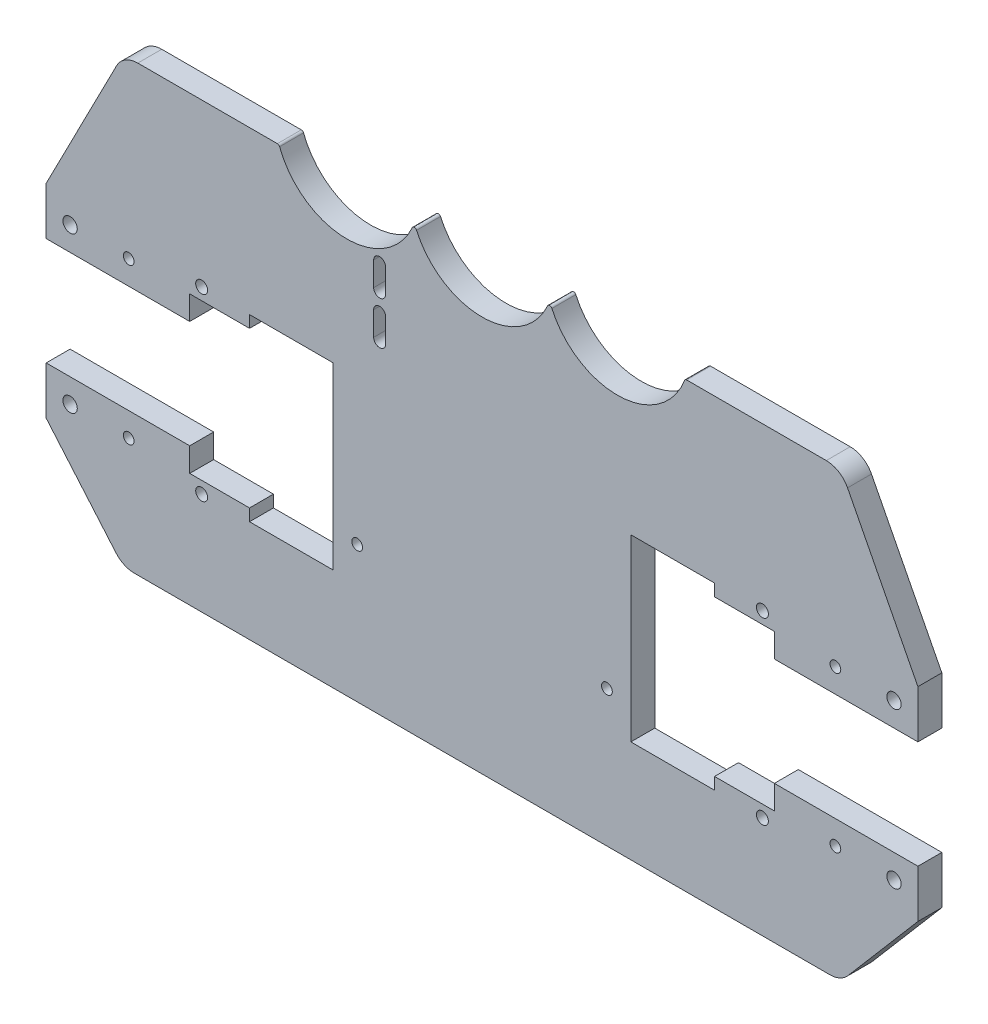
SolidWorks part; units mm, degrees
ref_plane "Plan de face" through (0, 0, 0) normal (0, 0, 1) x (1, 0, 0)
ref_plane "Plan de dessus" through (0, 0, 0) normal (0, 1, 0) x (1, 0, 0)
ref_plane "Plan de droite" through (0, 0, 0) normal (1, 0, 0) x (0, 0, -1)
sketch "Esquisse3" plane through (0, 0, 0) normal (0, 0, 1) x (1, 0, 0)
  line L0 (-182.2, 42.5) -> (-150, 105.2)
  line L1 (-182.2, 42.5) -> (182.2, 42.5)
  line L2 (-182.2, 42.5) -> (-182.2, -42.5)
  line L3 (-182.2, -42.5) -> (182.2, -42.5)
  line L4 (182.2, 42.5) -> (182.2, -42.5)
  line L5 (-150, 105.2) -> (150, 105.2)
  line L6 (-150, 105.2) -> (-150, 42.5)
  line L7 (-150, 42.5) -> (150, 42.5)
  line L8 (150, 105.2) -> (150, 42.5)
  line L9 (-150, -80.2) -> (150, -80.2)
  line L10 (-150, -80.2) -> (-150, -42.5)
  line L11 (-150, -42.5) -> (150, -42.5)
  line L12 (150, -80.2) -> (150, -42.5)
  line L13 (150, 105.2) -> (182.2, 42.5)
  line L14 (182.2, -42.5) -> (150, -80.2)
  line L15 (-150, -80.2) -> (-182.2, -42.5)
  dimension "D1" = 85
  dimension "D2" = 300
  dimension "D3" = 300
  dimension "D4" = 32.2
  dimension "D5" = 0
  dimension "D6" = 32.2
  dimension "D7" = 37.7
  dimension "D8" = 62.7
  dimension "D9" = 150
  dimension "D10" = 42.5
extrude "Boss.-Extru.1" add sketch "Esquisse3" along normal blind 10 contours L4 L1 L2 L3 | L8 L5 L6 L1 | L9 L12 L3 L10 | L6 L0 L1 | L15 L10 L3 | L14 L3 L12 | L13 L8 L1 region at (-160.7333, 63.4, 0) region at (0, 0, 0) region at (0, 73.85, 0) region at (-160.7333, -55.0667, 0) region at (160.7333, 63.4, 0) region at (0, -61.35, 0) region at (160.7333, -55.0667, 0)
sketch "Esquisse4" plane through (0, 0, 10) normal (0, 0, 1) x (1, 0, 0)
  line L1 (-182.2, 32.5) -> (-97.2, 32.5)
  line L2 (-182.2, 32.5) -> (-182.2, -32.5)
  line L3 (-182.2, -32.5) -> (-97.2, -32.5)
  line L4 (-97.2, 32.5) -> (-97.2, -32.5)
  line L5 (-97.2, -37.5) -> (-62.2, -37.5)
  line L6 (-97.2, -37.5) -> (-97.2, 37.5)
  line L7 (-97.2, 37.5) -> (-62.2, 37.5)
  line L8 (-62.2, -37.5) -> (-62.2, 37.5)
  line L9 (182.2, 32.5) -> (97.2, 32.5)
  line L10 (182.2, 32.5) -> (182.2, -32.5)
  line L11 (182.2, -32.5) -> (97.2, -32.5)
  line L12 (97.2, 32.5) -> (97.2, -32.5)
  line L13 (97.2, 37.5) -> (62.2, 37.5)
  line L14 (97.2, 37.5) -> (97.2, -37.5)
  line L15 (97.2, -37.5) -> (62.2, -37.5)
  line L16 (62.2, 37.5) -> (62.2, -37.5)
  line L17 (-182.2, 32.5) -> (-122.2, 32.5)
  line L18 (-182.2, 32.5) -> (-182.2, 22.5)
  line L19 (-182.2, 22.5) -> (-122.2, 22.5)
  line L20 (-122.2, 32.5) -> (-122.2, 22.5)
  line L21 (-182.2, -32.5) -> (-122.2, -32.5)
  line L22 (-182.2, -32.5) -> (-182.2, -22.5)
  line L23 (-182.2, -22.5) -> (-122.2, -22.5)
  line L24 (-122.2, -32.5) -> (-122.2, -22.5)
  line L25 (182.2, 32.5) -> (122.2, 32.5)
  line L26 (182.2, 32.5) -> (182.2, 22.5)
  line L27 (182.2, 22.5) -> (122.2, 22.5)
  line L28 (122.2, 32.5) -> (122.2, 22.5)
  line L29 (182.2, -32.5) -> (122.2, -32.5)
  line L30 (182.2, -32.5) -> (182.2, -22.5)
  line L31 (182.2, -22.5) -> (122.2, -22.5)
  line L32 (122.2, -32.5) -> (122.2, -22.5)
  line L34 (-182.2, 42.5) -> (-182.2, -42.5) construction
  line M16 (182.2, -42.5) -> (182.2, 42.5)
  line M20 (-182.2, 42.5) -> (-182.2, -42.5)
  dimension "D1" = 85
  dimension "D2" = 5
  dimension "D3" = 5
  dimension "D4" = 35
  dimension "D5" = 85
  dimension "D6" = 85
  dimension "D7" = 35
  dimension "D8" = 85
  dimension "D9" = 5
  dimension "D10" = 5
  dimension "D11" = 0
  dimension "D12" = 60
  dimension "D13" = 10
  dimension "D14" = 10
  dimension "D15" = 0
  dimension "D16" = 10
  dimension "D17" = 10
  dimension "D18" = 60
  dimension "D19" = 10
  dimension "D20" = 10
  dimension "D21" = 0
  dimension "D22" = 10
  dimension "D23" = 10
extrude "Enlèv. mat.-Extru.1" cut sketch "Esquisse4" against normal blind 10 contours L4 L1 L3 M20 | L5 L8 L7 L6 L4 | L13 L16 L15 L14 L12 | L9 L12 L11 M16 region at (-136.2318, 0, 10) region at (-79.7, 0, 10) region at (136.2318, 0, 10) region at (79.7, 0, 10)
sketch "Esquisse5" plane through (0, 0, 10) normal (0, 0, 1) x (1, 0, 0)
  line L1 (-150, 105.2) -> (150, 105.2) construction
  arc A0 (28.2843, 105.2) -> (-28.2843, 105.2) centre (0, 115.2) cw
  arc A1 (-28.2843, 105.2) -> (-84.8528, 105.2) centre (-56.5685, 115.2) cw
  arc A2 (28.2843, 105.2) -> (84.8528, 105.2) centre (56.5685, 115.2) ccw
  dimension "D1" = 10
  dimension "D2" = 30
  dimension "D3" = 30
  dimension "D6" = 30
  dimension "D4" = 10
  dimension "D5" = 10
extrude "Enlèv. mat.-Extru.2" cut sketch "Esquisse5" against normal blind 10 and the other way through all
sketch "Esquisse11" plane through (0, 0, 10) normal (0, 0, 1) x (1, 0, 0)
  line L0 (182.2, 42.5) -> (182.2, 22.5) construction
  line L1 (-182.2, 42.5) -> (-162.2, 42.5)
  line L2 (-182.2, 42.5) -> (-182.2, 22.5)
  line L3 (-182.2, 22.5) -> (-162.2, 22.5)
  line L4 (-162.2, 42.5) -> (-162.2, 22.5)
  line L6 (182.2, -22.5) -> (182.2, -42.5) construction
  line L7 (-182.2, -22.5) -> (-162.2, -22.5)
  line L8 (-182.2, -22.5) -> (-182.2, -42.5)
  line L9 (-182.2, -42.5) -> (-162.2, -42.5)
  line L10 (-162.2, -22.5) -> (-162.2, -42.5)
  line L11 (182.2, 22.5) -> (122.2, 22.5) construction
  line L12 (162.2, 42.5) -> (182.2, 42.5)
  line L13 (162.2, 42.5) -> (162.2, 22.5)
  line L14 (162.2, 22.5) -> (182.2, 22.5)
  line L15 (182.2, 42.5) -> (182.2, 22.5)
  line L16 (162.2, -22.5) -> (182.2, -22.5)
  line L17 (162.2, -22.5) -> (162.2, -42.5)
  line L18 (162.2, -42.5) -> (182.2, -42.5)
  line L19 (182.2, -22.5) -> (182.2, -42.5)
  line L20 (-182.2, -22.5) -> (-182.2, -42.5) construction
  line L22 (-182.2, 42.5) -> (-182.2, 22.5) construction
  line L23 (182.2, -22.5) -> (122.2, -22.5) construction
  line L24 (-182.2, -22.5) -> (-122.2, -22.5) construction
  line L25 (-182.2, 22.5) -> (-122.2, 22.5) construction
  point P24 (172.2, 22.5)
  dimension "D1" = 20
  dimension "D2" = 20
  dimension "D3" = 0
  dimension "D4" = 0
  dimension "D5" = 20
  dimension "D6" = 20
  dimension "D7" = 0
  dimension "D8" = 0
  dimension "D9" = 20
  dimension "D10" = 20
  dimension "D11" = 20
  dimension "D12" = 20
  dimension "D13" = 0
  dimension "D14" = 0
  dimension "D15" = 0
  dimension "D16" = 0
sketch "Esquisse10" plane through (0, 0, 10) normal (0, 0, 1) x (1, 0, 0)
  line L1 (-182.2, 42.5) -> (-162.2, 42.5) construction
  line L2 (162.2, -22.5) -> (162.2, -42.5) construction
  line L3 (-182.2, 22.5) -> (-162.2, 22.5) construction
  line L4 (-162.2, 42.5) -> (-162.2, 22.5) construction
  line L5 (-182.2, -22.5) -> (-182.2, -42.5) construction
  line L6 (-182.2, -22.5) -> (-162.2, -22.5) construction
  line L8 (162.2, 42.5) -> (182.2, 42.5) construction
  line L10 (162.2, 42.5) -> (162.2, 22.5) construction
  line L11 (182.2, -22.5) -> (182.2, -42.5) construction
  line L12 (162.2, -22.5) -> (182.2, -22.5) construction
  line L13 (162.2, -42.5) -> (182.2, -42.5) construction
  line L15 (-162.2, -22.5) -> (-162.2, -42.5) construction
  circle A1 centre (-147.7, 32.5) radius 2.25
  circle A2 centre (-172.2, 32.5) radius 3
  circle A3 centre (-172.2, -32.5) radius 3
  circle A4 centre (-147.7, -32.5) radius 2.25
  circle A6 centre (172.2, 32.5) radius 3
  circle A8 centre (147.7, 32.5) radius 2.25
  circle A9 centre (172.2, -32.5) radius 3
  circle A10 centre (147.7, -32.5) radius 2.25
  dimension "D4" = 4.5
  dimension "D9" = 6
  dimension "D10" = 6
  dimension "D17" = 6
  dimension "D18" = 4.5
  dimension "D24" = 4.5
  dimension "D28" = 6
  dimension "D35" = 4.5
  dimension "D15" = 14.5
  dimension "D16" = 14.5
  dimension "D5" = 14.5
  dimension "D13" = 14.5
  dimension "D6" = 10
  dimension "D7" = 10
  dimension "D8" = 10
  dimension "D11" = 10
  dimension "D12" = 10
  dimension "D14" = 10
  dimension "D22" = 10
  dimension "D23" = 10
  dimension "D27" = 10
  dimension "D29" = 10
  dimension "D30" = 10
  dimension "D34" = 10
extrude "Enlèv. mat.-Extru.3" cut sketch "Esquisse10" against normal blind 10
sketch "Esquisse13" plane through (0, 0, 10) normal (0, 0, 1) x (1, 0, 0)
  line L0 (-62.2, -37.5) -> (-62.2, 37.5) construction
  line L1 (-62, 1.8) -> (62, 1.8)
  line L2 (-62, 1.8) -> (-62, -8.2)
  line L3 (-62, -8.2) -> (62, -8.2)
  line L4 (62, 1.8) -> (62, -8.2)
  line L5 (62.2, 37.5) -> (62.2, -37.5) construction
  line L7 (-150, -80.2) -> (150, -80.2) construction
  dimension "D1" = 0.2
  dimension "D2" = 0.2
  dimension "D3" = 10
  dimension "D4" = 72
sketch "Esquisse15" plane through (0, 0, 10) normal (0, 0, 1) x (1, 0, 0)
  line L1 (-62.2, -37.5) -> (-62.2, 37.5) construction
  line L2 (62.2, 37.5) -> (62.2, -37.5) construction
  line L4 (-62, -8.2) -> (62, -8.2) construction
  circle A0 centre (-52.2, -23.2) radius 2.25
  circle A1 centre (52.2, -23.2) radius 2.25
  dimension "D1" = 4.5
  dimension "D2" = 4.5
  dimension "D4" = 15
  dimension "D3" = 15
  dimension "D5" = 10
  dimension "D6" = 10
extrude "Enlèv. mat.-Extru.4" cut sketch "Esquisse15" against normal blind 10
fillet "Congé1" radius 10 4 edges at (150, 105.2, 5) (150, -80.2, 5) (-150, 105.2, 5) (-150, -80.2, 5)
fillet "Congé3" radius 1 4 edges at (-84.8528, 105.2, 5) (-28.2843, 105.2, 5) (28.2843, 105.2, 5) (84.8528, 105.2, 5)
sketch "Esquisse16" plane through (0, 0, 10) normal (0, 0, 1) x (1, 0, 0)
  line L0 (-182.2, 42.5) -> (-182.2, 22.5) construction
  line L1 (-17.81, 59.2) -> (-27.81, 59.2)
  line L2 (-17.81, 59.2) -> (-17.81, 89.2)
  line L3 (-17.81, 89.2) -> (-27.81, 89.2)
  line L4 (-27.81, 59.2) -> (-27.81, 89.2)
  line L5 (-143.8939, 105.2) -> (-85.5513, 105.2) construction
  dimension "D1" = 154.39
  dimension "D2" = 16
  dimension "D3" = 30
  dimension "D4" = 10
sketch "Esquisse17" plane through (0, 0, 10) normal (0, 0, 1) x (1, 0, 0)
  line L0 (-42.81, 83.2) -> (-42.81, 73.2) construction
  line L1 (-40.31, 83.2) -> (-40.31, 73.2)
  line L2 (-45.31, 83.2) -> (-45.31, 73.2)
  line L3 (-42.81, 65.2) -> (-42.81, 55.2) construction
  line L4 (-40.31, 65.2) -> (-40.31, 55.2)
  line L5 (-45.31, 65.2) -> (-45.31, 55.2)
  line L6 (-27.81, 59.2) -> (-27.81, 89.2) construction
  line L7 (-17.81, 89.2) -> (-27.81, 89.2) construction
  line L8 (-17.81, 59.2) -> (-27.81, 59.2) construction
  arc A0 (-40.31, 83.2) -> (-45.31, 83.2) centre (-42.81, 83.2) ccw
  arc A1 (-45.31, 73.2) -> (-40.31, 73.2) centre (-42.81, 73.2) ccw
  arc A2 (-40.31, 65.2) -> (-45.31, 65.2) centre (-42.81, 65.2) ccw
  arc A3 (-45.31, 55.2) -> (-40.31, 55.2) centre (-42.81, 55.2) ccw
  point P2 (-42.81, 78.2)
  point P7 (-42.81, 60.2)
  dimension "D6" = 2.5
  dimension "D7" = 2.5
  dimension "D1" = 15
  dimension "D2" = 6
  dimension "D3" = 6
  dimension "D4" = 10
  dimension "D5" = 10
extrude "Enlèv. mat.-Extru.5" cut sketch "Esquisse17" against normal blind 10
sketch "Esquisse18" plane through (0, 0, 10) normal (0, 0, 1) x (1, 0, 0)
  line L1 (122.2, -32.5) -> (97.2, -32.5) construction
  line L2 (182.2, 42.5) -> (182.2, 22.5) construction
  line L3 (182.2, -22.5) -> (182.2, -42.5) construction
  line L4 (-182.2, 42.5) -> (-182.2, 22.5) construction
  line L5 (-182.2, -22.5) -> (-182.2, -42.5) construction
  line L6 (-122.2, -32.5) -> (-97.2, -32.5) construction
  circle A0 centre (117.2, -37.5) radius 2.5
  circle A1 centre (117.2, 37.5) radius 2.5
  circle A2 centre (-117.2, -37.5) radius 2.5
  circle A3 centre (-117.2, 37.5) radius 2.5
  dimension "D1" = 5
  dimension "D2" = 5
  dimension "D3" = 75
  dimension "D4" = 5
  dimension "D5" = 65
  dimension "D6" = 65
  dimension "D7" = 5
  dimension "D8" = 5
  dimension "D9" = 65
  dimension "D10" = 65
  dimension "D11" = 75
  dimension "D12" = 5
extrude "Enlèv. mat.-Extru.6" cut sketch "Esquisse18" against normal blind 10
